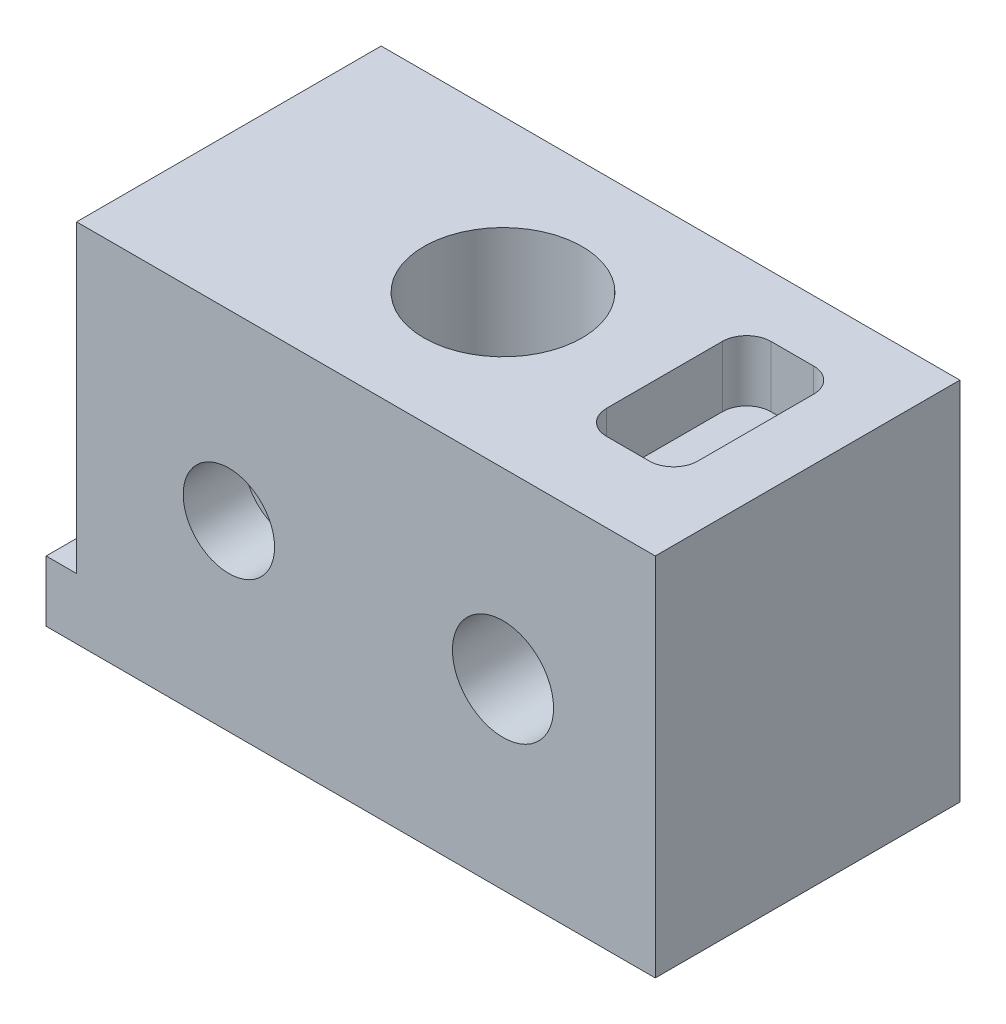
SolidWorks part; units mm, degrees
material "6061 Alloy"
ref_plane "Front Plane" through (0, 0, 0) normal (0, 0, 1) x (1, 0, 0)
ref_plane "Top Plane" through (0, 0, 0) normal (0, 1, 0) x (1, 0, 0)
ref_plane "Right Plane" through (0, 0, 0) normal (1, 0, 0) x (0, 0, -1)
sketch "Sketch1" plane through (0, 0, 0) normal (0, 1, 0) x (1, 0, 0)
  line L1 (-50, -25) -> (50, -25)
  line L2 (-50, -25) -> (-50, 25)
  line L3 (-50, 25) -> (50, 25)
  line L4 (50, -25) -> (50, 25)
  line L5 (-50, -25) -> (50, 25) construction
  line L6 (-50, 25) -> (50, -25) construction
  point P0 (0, 0)
  dimension "D1" = 100
  dimension "D2" = 50
extrude "Boss-Extrude1" add sketch "Sketch1" along normal blind 60
sketch "Sketch2" plane through (0, 60, 0) normal (0, 1, 0) x (1, 0, 0)
  line L0 (-50, -25) -> (50, -25) construction
  line L1 (-50, 25) -> (-45, 25)
  line L2 (-50, 25) -> (-50, -25)
  line L3 (-50, -25) -> (-45, -25)
  line L4 (-45, 25) -> (-45, -25)
  dimension "D1" = 5
extrude "Cut-Extrude1" cut sketch "Sketch2" against normal blind 50
sketch "Sketch3" plane through (0, 60, 0) normal (0, 1, 0) x (1, 0, 0)
  circle A0 centre (0, 0) radius 13
  dimension "D1" = 26
extrude "Cut-Extrude2" cut sketch "Sketch3" against normal blind 50
sketch "Sketch4" plane through (0, 0, 25) normal (0, 0, 1) x (1, 0, 0)
  line L0 (-50, 0) -> (50, 0) construction
  line L1 (50, 60) -> (50, 0) construction
  circle A0 centre (25, 30) radius 8.302
  dimension "D1" = 30
  dimension "D2" = 25
extrude "Cut-Extrude3" cut sketch "Sketch4" against normal through all
sketch "Sketch6" plane through (0, 60, 0) normal (0, 1, 0) x (1, 0, 0)
  line L0 (-45, -25) -> (50, -25) construction
  line L1 (29, 15) -> (36, 15)
  line L2 (25, 11) -> (25, -8)
  line L3 (29, -12) -> (36, -12)
  line L4 (40, 11) -> (40, -8)
  line L5 (50, -25) -> (50, 25) construction
  arc A0 (25, -8) -> (29, -12) centre (29, -8) ccw
  arc A1 (36, -12) -> (40, -8) centre (36, -8) ccw
  arc A2 (40, 11) -> (36, 15) centre (36, 11) ccw
  arc A3 (29, 15) -> (25, 11) centre (29, 11) ccw
  dimension "D1" = 4
  dimension "D2" = 10
  dimension "D3" = 13
  dimension "D4" = 10
  dimension "D5" = 15
extrude "Cut-Extrude4" cut sketch "Sketch6" against normal blind 10
sketch "Sketch7" plane through (0, 0, 25) normal (0, 0, 1) x (1, 0, 0)
  line L0 (25, 30) -> (-20, 30) construction
  circle A0 centre (-20, 30) radius 7.5
  dimension "D1" = 15
  dimension "D2" = 45
extrude "Cut-Extrude5" cut sketch "Sketch7" against normal blind 10
